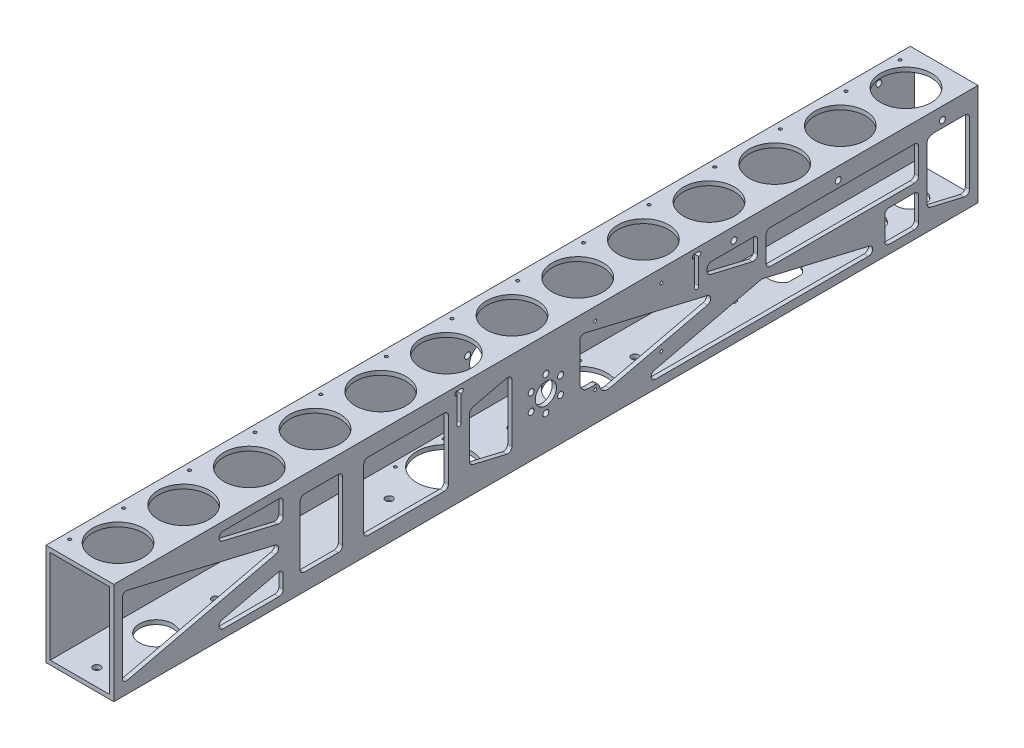
SolidWorks part; units mm, degrees
material "6061-T6 (SS)"
ref_plane "Front Plane" through (0, 0, 0) normal (0, 0, 1) x (1, 0, 0)
ref_plane "Top Plane" through (0, 0, 0) normal (0, 1, 0) x (1, 0, 0)
ref_plane "Right Plane" through (0, 0, 0) normal (1, 0, 0) x (0, 0, -1)
sketch "Sketch1" plane through (0, 0, 0) normal (0, 0, 1) x (1, 0, 0)
  line L0 (3.175, 3.175) -> (3.175, 73.025)
  line L1 (0, 0) -> (50.8, 0)
  line L2 (0, 0) -> (0, 76.2)
  line L3 (0, 76.2) -> (50.8, 76.2)
  line L4 (50.8, 0) -> (50.8, 76.2)
  line L5 (3.175, 73.025) -> (47.625, 73.025)
  line L6 (47.625, 3.175) -> (47.625, 73.025)
  line L7 (3.175, 3.175) -> (47.625, 3.175)
  dimension "D1" = 76.2
  dimension "D2" = 50.8
  dimension "D3" = 3.175
extrude "Boss-Extrude1" add sketch "Sketch1" along normal blind 647.7
sketch "Sketch2" plane through (50.8, 0, 0) normal (1, 0, 0) x (0, 0, -1)
  line L0 (-323.85, 76.2) -> (-323.85, 0) construction
  line L1 (-647.7, 76.2) -> (0, 76.2) construction
  line L2 (-647.7, 0) -> (0, 0) construction
  line L3 (-121.0655, 35.0094) -> (-10.2522, 8.9357)
  line L4 (-322.3956, 82.3812) -> (1.4544, 6.1812) construction
  line L5 (-649.1544, 6.1812) -> (-325.3044, 82.3812) construction
  line L6 (-646.2456, 82.3812) -> (-322.3956, 6.1812) construction
  line L7 (-649.1544, 70.0188) -> (-325.3044, -6.1812) construction
  line L8 (-647.7, 76.2) -> (-323.85, 0) construction
  line L9 (-647.7, 0) -> (-323.85, 76.2) construction
  line L10 (-323.85, 76.2) -> (0, 0) construction
  line L11 (-323.85, 0) -> (0, 76.2) construction
  line L12 (-6.35, 6.35) -> (-6.35, 69.85)
  line L13 (-6.35, 69.85) -> (-641.35, 69.85)
  line L14 (-641.35, 69.85) -> (-641.35, 6.35)
  line L15 (-641.35, 6.35) -> (-6.35, 6.35)
  line L16 (-6.35, 12.0263) -> (-6.35, 64.1737)
  line L17 (-646.2456, -6.1812) -> (-322.3956, 70.0188) construction
  line L18 (-641.35, 64.1737) -> (-641.35, 12.0263)
  line L19 (-641.35, 6.35) -> (-620.7125, 6.35)
  line L20 (-322.3956, -6.1812) -> (1.4544, 70.0188) construction
  line L21 (-325.3044, 6.1812) -> (-1.4544, 82.3812) construction
  line L22 (-161.1978, 44.7945) -> (-81.3408, 63.5844)
  line L23 (-161.1978, 31.4055) -> (-81.3408, 12.6156)
  line L24 (-241.782, 69.85) -> (-82.068, 69.85)
  line L25 (-647.7, 69.85) -> (0, 69.85)
  line L26 (-641.35, 69.85) -> (-620.7125, 69.85)
  line L27 (-241.782, 6.35) -> (-82.068, 6.35)
  line L28 (-566.3592, 63.5844) -> (-486.5022, 44.7945)
  line L29 (-637.4478, 67.2643) -> (-526.6345, 41.1906)
  line L30 (-637.4478, 8.9357) -> (-526.6345, 35.0094)
  line L31 (-566.3592, 12.6156) -> (-486.5022, 31.4055)
  line L32 (-242.5092, 63.5844) -> (-162.6522, 44.7945)
  line L33 (-325.3044, 70.0188) -> (-323.85, 69.6766)
  line L34 (-294.5478, 13.418) -> (-202.7845, 35.0094)
  line L35 (-242.5092, 12.6156) -> (-162.6522, 31.4055)
  line L36 (-349.25, 59.6914) -> (-349.25, 16.5086)
  line L37 (-298.45, 59.6914) -> (-298.45, 16.5086)
  line L38 (-294.5478, 62.782) -> (-202.7845, 41.1906)
  line L39 (-121.0655, 41.1906) -> (-10.2522, 67.2643)
  line L40 (-325.3044, 70.0188) -> (-1.4544, -6.1812) construction
  line L41 (-485.0478, 44.7945) -> (-405.1908, 63.5844)
  line L42 (-444.9155, 35.0094) -> (-353.1522, 13.418)
  line L43 (-444.9155, 41.1906) -> (-353.1522, 62.782)
  line L44 (-485.0478, 31.4055) -> (-405.1908, 12.6156)
  line L45 (-565.632, 69.85) -> (-405.918, 69.85)
  line L46 (-565.632, 6.35) -> (-405.918, 6.35)
  line L47 (-26.9875, 6.35) -> (-6.35, 6.35)
  line L48 (-26.9875, 69.85) -> (-6.35, 69.85)
  arc A0 (-405.918, 6.35) -> (-405.1908, 12.6156) centre (-405.918, 9.525) ccw
  arc A1 (-565.632, 6.35) -> (-566.3592, 12.6156) centre (-565.632, 9.525) cw
  arc A2 (-641.35, 64.1737) -> (-637.4478, 67.2643) centre (-638.175, 64.1737) cw
  arc A3 (-637.4478, 8.9357) -> (-641.35, 12.0263) centre (-638.175, 12.0263) cw
  arc A4 (-82.068, 6.35) -> (-81.3408, 12.6156) centre (-82.068, 9.525) ccw
  arc A5 (-241.782, 6.35) -> (-242.5092, 12.6156) centre (-241.782, 9.525) cw
  arc A6 (-6.35, 12.0263) -> (-10.2522, 8.9357) centre (-9.525, 12.0263) cw
  arc A7 (-6.35, 64.1737) -> (-10.2522, 67.2643) centre (-9.525, 64.1737) ccw
  arc A8 (-81.3408, 63.5844) -> (-82.068, 69.85) centre (-82.068, 66.675) ccw
  arc A9 (-242.5092, 63.5844) -> (-241.782, 69.85) centre (-241.782, 66.675) cw
  arc A10 (-121.0655, 41.1906) -> (-121.0655, 35.0094) centre (-120.3383, 38.1) ccw
  arc A11 (-161.1978, 31.4055) -> (-162.6522, 31.4055) centre (-161.925, 28.3149) ccw
  arc A12 (-161.1978, 44.7945) -> (-162.6522, 44.7945) centre (-161.925, 47.8851) cw
  arc A13 (-202.7845, 35.0094) -> (-202.7845, 41.1906) centre (-203.5117, 38.1) ccw
  arc A14 (-294.5478, 13.418) -> (-298.45, 16.5086) centre (-295.275, 16.5086) cw
  arc A15 (-294.5478, 62.782) -> (-298.45, 59.6914) centre (-295.275, 59.6914) ccw
  arc A16 (-353.1522, 62.782) -> (-349.25, 59.6914) centre (-352.425, 59.6914) cw
  arc A17 (-349.25, 16.5086) -> (-353.1522, 13.418) centre (-352.425, 16.5086) cw
  arc A18 (-485.0478, 31.4055) -> (-486.5022, 31.4055) centre (-485.775, 28.3149) ccw
  arc A19 (-526.6345, 35.0094) -> (-526.6345, 41.1906) centre (-527.3617, 38.1) ccw
  arc A20 (-444.9155, 35.0094) -> (-444.9155, 41.1906) centre (-444.1883, 38.1) cw
  arc A21 (-485.0478, 44.7945) -> (-486.5022, 44.7945) centre (-485.775, 47.8851) cw
  arc A22 (-405.1908, 63.5844) -> (-405.918, 69.85) centre (-405.918, 66.675) ccw
  arc A23 (-566.3592, 63.5844) -> (-565.632, 69.85) centre (-565.632, 66.675) cw
  point P69 (-592.988, 6.35)
  point P92 (-161.925, 44.6234)
  point P99 (-298.45, 63.7001)
  point P106 (-485.775, 31.5766)
  point P111 (-458.0505, 38.1)
  point P118 (-592.988, 69.85)
  dimension "D13" = 3.175
  dimension "D11" = 25.4
  dimension "D12" = 25.4
  dimension "D1" = 6.35
  dimension "D2" = 6.35
  dimension "D3" = 6.35
  dimension "D4" = 6.35
  dimension "D5" = 6.35
  dimension "D6" = 6.35
  dimension "D7" = 6.35
  dimension "D8" = 6.35
  dimension "D9" = 6.35
  dimension "D10" = 6.35
extrude "Cut-Extrude1" cut sketch "Sketch2" against normal through all contours A23 L28 A21 L41 A22 L45 | L30 A19 L29 A2 L18 A3 | L44 A18 L31 A1 L46 A0 | A20 L42 A17 L36 A16 L43 | L38 A15 L37 A14 L34 A13 | A12 L22 A8 L24 A9 L32 | L23 A11 L35 A5 L27 A4 | L39 A10 L3 A6 L16 A7
sketch "Sketch3" plane through (0, 76.2, 0) normal (0, 1, 0) x (1, 0, 0)
  line L0 (50.8, -647.7) -> (0, -647.7) construction
  line L1 (0, -647.7) -> (0, 0) construction
  circle A0 centre (25.4, -603.25) radius 19.05
  circle A1 centre (25.4, -552.45) radius 19.05
  circle A6 centre (25.4, -298.45) radius 19.05
  circle A7 centre (25.4, -247.65) radius 19.05
  circle A8 centre (25.4, -196.85) radius 19.05
  circle A10 centre (25.4, -95.25) radius 19.05
  circle A11 centre (25.4, -44.45) radius 19.05
  circle A12 centre (25.4, -501.65) radius 19.05
  circle A13 centre (25.4, -146.05) radius 19.05
  circle A14 centre (25.4, -349.25) radius 19.05
  circle A15 centre (25.4, -400.05) radius 19.05
  circle A16 centre (25.4, -450.85) radius 19.05
  dimension "D1" = 38.1
  dimension "D2" = 44.45
  dimension "D3" = 25.4
  dimension "D4" = 12
extrude "Cut-Extrude2" [suppressed] cut sketch "Sketch3" against normal through all
sketch "Sketch4" plane through (50.8, 0, 0) normal (1, 0, 0) x (0, 0, -1)
  line L0 (-647.7, 76.2) -> (0, 76.2) construction
  line L1 (-323.85, 76.2) -> (-323.85, 0) construction
  line L2 (-647.7, 0) -> (0, 0) construction
  circle A0 centre (-323.85, 38.1) radius 7.9375
  dimension "D2" = 15.875
  dimension "D1" = 38.1
extrude "Cut-Extrude3" cut sketch "Sketch4" against normal through all
sketch "Sketch5" plane through (0, 0, 0) normal (-1, 0, 0) x (0, 0, 1)
  circle A0 centre (323.85, 38.1) radius 9.525
  dimension "D1" = 19.05
extrude "Cut-Extrude4" cut sketch "Sketch5" against normal up to next
hole_wizard "#8 Clearance Hole1" positions "Sketch7" profile "Sketch6" hole size "#8" standard "Ansi Inch" end condition through all
sketch "Sketch7" plane through (0, 0, 0) normal (-1, 0, 0) x (0, 0, 1)
  line L0 (647.7, 76.2) -> (0, 76.2) construction
  line L1 (323.85, 76.2) -> (323.85, 0) construction
  line L2 (647.7, 0) -> (0, 0) construction
  circle A0 centre (323.85, 38.1) radius 9.525 construction
  point P0 (323.85, 50.8)
  point P15 (323.85, 76.2)
  dimension "D1" = 12.7
sketch "Sketch6" plane through (0, 50.8, 323.85) normal (0, 1, 0) x (0, 0, 1)
  line L0 (0, 0) -> (0, 50.8)
  line L1 (0, 50.8) -> (2.2479, 50.8)
  line L2 (2.2479, 50.8) -> (2.2479, 0)
  line L5 (2.2479, 0) -> (0, 0)
  line L11 (0, -6.35) -> (0, 107.95) construction
  dimension "Thru Hole Dia." = 4.4958
  dimension "Thru Hole Depth" = 50.8
pattern_circular "CirPattern1" count 6 over 360 about axis through (0, 38.1, 323.85) along (1, 0, 0) of "#8 Clearance Hole1"
hole_wizard "1/4-28 Tapped Hole1" positions "Sketch9" profile "Sketch8" tap size "1/4-28" standard "Ansi Inch"
sketch "Sketch9" plane through (0, 76.2, 0) normal (0, 1, 0) x (-1, 0, 0)
  line L0 (-25.4, 647.7) -> (-25.4, 0) construction
  line L1 (-50.8, 647.7) -> (0, 647.7) construction
  line L2 (-50.8, 0) -> (0, 0) construction
  point P0 (-25.4, 498.475)
  point P1 (-25.4, 323.85)
  point P5 (-25.4, 149.225)
  point P20 (-25.4, 323.85)
  dimension "D1" = 149.225
  dimension "D2" = 149.225
sketch "Sketch8" plane through (25.4, 76.2, 498.475) normal (1, 0, 0) x (0, 0, 1)
  line L0 (0, 0) -> (0, 76.2)
  line L1 (0, 76.2) -> (2.7051, 76.2)
  line L2 (2.7051, 76.2) -> (2.7051, 0)
  line L5 (2.7051, 0) -> (0, 0)
  line L11 (0, -6.35) -> (0, 107.95) construction
  dimension "Thru Tap Drill Dia." = 5.4102
  dimension "Thru Tap Drill Depth" = 76.2
cosmetic thread "Hole Thread1" [suppressed]
cosmetic thread "Hole Thread2" [suppressed]
cosmetic thread "Hole Thread3" [suppressed]
sketch "Sketch10" plane through (50.8, 0, 0) normal (1, 0, 0) x (0, 0, -1)
  line L0 (-647.7, 0) -> (0, 0) construction
  line L1 (-520.7, 0) -> (-463.55, 0)
  line L2 (-520.7, 0) -> (-520.7, 76.2)
  line L3 (-520.7, 76.2) -> (-463.55, 76.2)
  line L4 (-463.55, 0) -> (-463.55, 76.2)
  line L5 (-647.7, 76.2) -> (0, 76.2) construction
  line L6 (-647.7, 0) -> (-647.7, 76.2) construction
  dimension "D1" = 127
  dimension "D2" = 57.15
extrude "Boss-Extrude2" add sketch "Sketch10" against normal blind 3.175
sketch "Sketch12" plane through (0, 76.2, 0) normal (0, 1, 0) x (1, 0, 0)
  line L0 (0, -647.7) -> (0, 0) construction
  line L1 (7.1374, -291.3126) -> (43.6626, -291.3126) construction
  line L2 (7.1374, -291.3126) -> (7.1374, -254.7874) construction
  line L3 (7.1374, -254.7874) -> (43.6626, -254.7874) construction
  line L4 (43.6626, -291.3126) -> (43.6626, -254.7874) construction
  line L5 (7.1374, -291.3126) -> (43.6626, -254.7874) construction
  line L6 (7.1374, -254.7874) -> (43.6626, -291.3126) construction
  line L9 (50.8, 0) -> (0, 0) construction
  line L10 (7.1374, -392.9126) -> (43.6626, -392.9126) construction
  line L11 (7.1374, -392.9126) -> (7.1374, -356.3874) construction
  line L12 (7.1374, -356.3874) -> (43.6626, -356.3874) construction
  line L13 (43.6626, -392.9126) -> (43.6626, -356.3874) construction
  line L14 (7.1374, -392.9126) -> (43.6626, -356.3874) construction
  line L15 (7.1374, -356.3874) -> (43.6626, -392.9126) construction
  line L16 (7.1374, -323.85) -> (43.6626, -323.85) construction
  line L17 (25.4, -293.497) -> (25.4, -354.203) construction
  line L19 (25.4, 25.4) -> (25.4, -622.3) construction
  line L20 (25.4, -76.2) -> (25.4, -723.9) construction
  circle A0 centre (25.4, -273.05) radius 20.447
  circle A1 centre (25.4, -374.65) radius 20.447
  point P0 (25.4, -273.05)
  point P5 (25.4, -323.85)
  point P15 (25.4, -374.65)
  dimension "D3" = 40.894
  dimension "D5" = 25.4
  dimension "D7" = 323.85
  dimension "D1" = 36.5252
  dimension "D2" = 36.5252
  dimension "D6" = 101.6
  dimension "D4" = 2
sketch "Sketch17" plane through (50.8, 0, 0) normal (1, 0, 0) x (0, 0, -1)
  line L0 (-492.125, 76.2) -> (-492.125, 0) construction
  line L1 (-647.7, 76.2) -> (0, 76.2) construction
  line L2 (-647.7, 0) -> (0, 0) construction
  line L3 (-647.7, 0) -> (-647.7, 76.2) construction
  line L6 (-508, 12.7) -> (-476.25, 12.7)
  line L7 (-508, 12.7) -> (-508, 63.5)
  line L8 (-508, 63.5) -> (-476.25, 63.5)
  line L9 (-476.25, 12.7) -> (-476.25, 63.5)
  line L10 (-508, 12.7) -> (-476.25, 63.5) construction
  line L11 (-508, 63.5) -> (-476.25, 12.7) construction
  point P8 (-492.125, 38.1)
  dimension "D1" = 139.7
  dimension "D2" = 50.8
  dimension "D3" = 31.75
extrude "Cut-Extrude6" cut sketch "Sketch17" against normal up to next
sketch "Sketch18" plane through (0, 76.2, 0) normal (0, 1, 0) x (1, 0, 0)
  line L0 (25.4, 0) -> (25.4, -647.7) construction
  line L1 (50.8, 0) -> (0, 0) construction
  line L2 (50.8, -647.7) -> (0, -647.7) construction
  line L3 (34.4043, -115.4433) -> (34.4043, -125.8567)
  arc A0 (34.4043, -115.4433) -> (34.4043, -125.8567) centre (25.4, -120.65) ccw
  dimension "D1" = 20.8026
  dimension "D2" = 120.65
  dimension "D3" = 9.0043
sketch "Sketch19" plane through (0, 76.2, 0) normal (0, 1, 0) x (1, 0, 0)
  line L0 (50.8, -647.7) -> (50.8, 0) construction
  line L1 (15.24, -9.525) -> (35.56, -9.525)
  line L2 (8.89, -15.875) -> (8.89, -130.175)
  line L3 (15.24, -136.525) -> (35.56, -136.525)
  line L4 (41.91, -15.875) -> (41.91, -130.175)
  line L5 (0, -647.7) -> (0, 0) construction
  arc A0 (35.56, -136.525) -> (41.91, -130.175) centre (35.56, -130.175) ccw
  arc A1 (8.89, -130.175) -> (15.24, -136.525) centre (15.24, -130.175) ccw
  arc A2 (35.56, -9.525) -> (41.91, -15.875) centre (35.56, -15.875) cw
  arc A3 (15.24, -9.525) -> (8.89, -15.875) centre (15.24, -15.875) ccw
  point P12 (41.91, -136.525)
  point P17 (41.91, -9.525)
  dimension "D5" = 6.35
  dimension "D3" = 15.875
  dimension "D1" = 8.89
  dimension "D2" = 8.89
  dimension "D4" = 127
ref_plane "Plane1" through (0, 38.1, 0) normal (0, 1, 0) x (-1, 0, 0)
sketch "Sketch20" [suppressed] plane through (0, 0, 0) normal (0, -1, 0) x (1, 0, 0)
  line L0 (25.4, 647.7) -> (25.4, 498.475) construction
  line L1 (0, 647.7) -> (50.8, 647.7) construction
  line L3 (13.0937, 603.6437) -> (37.7063, 603.6437) construction
  line L4 (13.0937, 603.6437) -> (13.0937, 628.2563) construction
  line L5 (13.0937, 628.2563) -> (37.7063, 628.2563) construction
  line L6 (37.7063, 603.6437) -> (37.7063, 628.2563) construction
  line L7 (13.0937, 603.6437) -> (37.7063, 628.2563) construction
  line L8 (13.0937, 628.2563) -> (37.7063, 603.6437) construction
  circle A0 centre (25.4, 615.95) radius 12.4333
  point P5 (25.4, 615.95)
  dimension "D3" = 24.8666
  dimension "D1" = 24.6126
  dimension "D2" = 24.6126
  dimension "D4" = 31.75
sketch "Sketch21" plane through (0, 0, 0) normal (0, -1, 0) x (1, 0, 0)
  circle A0 centre (25.4, 374.65) radius 20.447 construction
  circle A1 centre (25.4, 273.05) radius 20.447 construction
  circle A2 centre (25.4, 374.65) radius 20.447
  circle A3 centre (25.4, 273.05) radius 20.447
extrude "Cut-Extrude10" cut sketch "Sketch21" against normal up to next
hole_wizard "#4-40 Tapped Hole1" positions "Sketch23" profile "Sketch22" tap size "#4-40" standard "Ansi Inch" end condition up to next
sketch "Sketch23" plane through (0, 0, 0) normal (0, -1, 0) x (1, 0, 0)
  point P1 (7.1374, 392.9126)
  point P4 (43.6626, 392.9126)
  point P7 (7.1374, 356.3874)
  point P10 (43.6626, 356.3874)
  point P13 (7.1374, 291.3126)
  point P16 (43.6626, 291.3126)
  point P19 (7.1374, 254.7874)
  point P22 (43.6626, 254.7874)
cosmetic thread "Hole Thread4"
cosmetic thread "Hole Thread5"
cosmetic thread "Hole Thread6"
cosmetic thread "Hole Thread7"
cosmetic thread "Hole Thread8"
cosmetic thread "Hole Thread9"
cosmetic thread "Hole Thread10"
cosmetic thread "Hole Thread11"
sketch "Sketch22" plane through (7.1374, 0, 392.9126) normal (1, 0, 0) x (0, 0, -1)
  line L0 (0, 0) -> (0, 3.175)
  line L1 (0, 3.175) -> (1.1303, 3.175)
  line L2 (1.1303, 3.175) -> (1.1303, 0)
  line L5 (1.1303, 0) -> (0, 0)
  line L11 (0, -6.35) -> (0, 107.95) construction
  dimension "Thru Tap Drill Dia." = 2.2606
  dimension "Thru Tap Drill Depth" = 3.175
sketch "Sketch24" plane through (0, 0, 0) normal (0, -1, 0) x (1, 0, 0)
  line L0 (34.4043, 115.4433) -> (34.4043, 125.8567) construction
  line L1 (34.4043, 115.4433) -> (34.4043, 125.8567)
  arc A0 (34.4043, 125.8567) -> (34.4043, 115.4433) centre (25.4, 120.65) ccw construction
  arc A1 (34.4043, 125.8567) -> (34.4043, 115.4433) centre (25.4, 120.65) ccw
extrude "Cut-Extrude11" cut sketch "Sketch24" against normal up to next
pattern_linear "LPattern1" count 4 spacing 31.75 along (0, 0, -1) of "Cut-Extrude11"
sketch "Sketch25" plane through (0, 0, 0) normal (0, -1, 0) x (1, 0, 0)
  line L0 (15.24, 136.525) -> (35.56, 136.525) construction
  line L1 (8.89, 15.875) -> (8.89, 130.175) construction
  line L2 (15.24, 9.525) -> (35.56, 9.525) construction
  line L3 (41.91, 15.875) -> (41.91, 130.175) construction
  line L4 (0, 0) -> (50.8, 0)
  line L5 (50.8, 0) -> (50.8, 647.7)
  line L6 (50.8, 647.7) -> (0, 647.7)
  line L7 (0, 647.7) -> (0, 0)
  line L8 (0, 0) -> (50.8, 0)
  line L9 (50.8, 0) -> (50.8, 647.7)
  line L10 (50.8, 647.7) -> (0, 647.7)
  line L11 (0, 647.7) -> (0, 0)
  line L12 (15.24, 136.525) -> (35.56, 136.525)
  line L13 (8.89, 15.875) -> (8.89, 130.175)
  line L14 (15.24, 9.525) -> (35.56, 9.525)
  line L15 (41.91, 15.875) -> (41.91, 130.175)
  arc A0 (15.24, 136.525) -> (8.89, 130.175) centre (15.24, 130.175) ccw construction
  arc A1 (8.89, 15.875) -> (15.24, 9.525) centre (15.24, 15.875) ccw construction
  arc A2 (35.56, 9.525) -> (41.91, 15.875) centre (35.56, 15.875) ccw construction
  arc A3 (41.91, 130.175) -> (35.56, 136.525) centre (35.56, 130.175) ccw construction
  arc A4 (15.24, 136.525) -> (8.89, 130.175) centre (15.24, 130.175) ccw
  arc A5 (8.89, 15.875) -> (15.24, 9.525) centre (15.24, 15.875) ccw
  arc A6 (35.56, 9.525) -> (41.91, 15.875) centre (35.56, 15.875) ccw
  arc A7 (41.91, 130.175) -> (35.56, 136.525) centre (35.56, 130.175) ccw
  dimension "D1" = 0
extrude "Cut-Extrude12" cut sketch "Sketch25" against normal blind 1.5875 flip side to cut
hole_wizard "1/4-28 Tapped Hole2" positions "Sketch27" profile "Sketch26" tap size "1/4-28" standard "Ansi Inch" end condition up to next
sketch "Sketch27" plane through (14.4115, 0, -20.3004) normal (0, -1, 0) x (1, 0, 0)
  line L0 (10.9885, 20.3004) -> (10.9885, 668.0004) construction
  line L3 (-14.4115, 668.0004) -> (36.3885, 668.0004) construction
  line L4 (-14.4115, 20.3004) -> (36.3885, 20.3004) construction
  line L5 (-14.4115, 668.0004) -> (-14.4115, 20.3004) construction
  point P10 (10.9885, 179.0504)
  point P12 (10.9885, 252.0754)
  point P14 (10.9885, 344.1504)
  point P16 (10.9885, 436.2254)
  point P18 (10.9885, 566.4004)
  point P20 (10.9885, 655.3004)
  dimension "D1" = 158.75
  dimension "D2" = 73.025
  dimension "D3" = 92.075
  dimension "D4" = 130.175
  dimension "D5" = 88.9
  dimension "D6" = 25.4
sketch "Sketch26" plane through (25.4, 0, 158.75) normal (1, 0, 0) x (0, 0, -1)
  line L0 (0, 0) -> (0, 3.175)
  line L1 (0, 3.175) -> (2.7051, 3.175)
  line L2 (2.7051, 3.175) -> (2.7051, 0)
  line L5 (2.7051, 0) -> (0, 0)
  line L11 (0, -6.35) -> (0, 107.95) construction
  dimension "Thru Tap Drill Dia." = 5.4102
  dimension "Thru Tap Drill Depth" = 3.175
cosmetic thread "Hole Thread18"
cosmetic thread "Hole Thread19"
cosmetic thread "Hole Thread20"
cosmetic thread "Hole Thread22"
cosmetic thread "Hole Thread23"
cosmetic thread "Hole Thread24"
sketch "Sketch28" plane through (0, 0, 0) normal (0, -1, 0) x (1, 0, 0)
  line L1 (0, 647.7) -> (0, 0) construction
  circle A0 centre (25.4, 195.2625) radius 19.05
  circle A1 centre (25.4, 455.6125) radius 19.05
  circle A2 centre (25.4, 506.4125) radius 19.05
  circle A3 centre (25.4, 590.55) radius 19.05
  circle A6 centre (25.4, 635) radius 2.7051 construction
  circle A8 centre (25.4, 546.1) radius 2.7051 construction
  circle A9 centre (25.4, 231.775) radius 2.7051 construction
  dimension "D1" = 38.1
  dimension "D5" = 39.6875
  dimension "D2" = 44.45
  dimension "D3" = 25.4
  dimension "D4" = 50.8
  dimension "D6" = 36.5125
extrude "Cut-Extrude13" cut sketch "Sketch28" against normal up to next
sketch "Sketch29" plane through (0, 76.2, 0) normal (0, 1, 0) x (1, 0, 0)
  line L0 (0, -647.7) -> (0, 0) construction
  line L1 (50.8, 0) -> (0, 0) construction
  circle A0 centre (25.4, -28.575) radius 19.05
  circle A1 centre (25.4, -77.7875) radius 19.05
  circle A2 centre (25.4, -127) radius 19.05
  circle A3 centre (25.4, -176.2125) radius 19.05
  circle A4 centre (25.4, -225.425) radius 19.05
  circle A5 centre (25.4, -274.6375) radius 19.05
  circle A6 centre (25.4, -323.85) radius 19.05
  circle A7 centre (25.4, -373.0625) radius 19.05
  circle A8 centre (25.4, -422.275) radius 19.05
  circle A9 centre (25.4, -471.4875) radius 19.05
  circle A10 centre (25.4, -520.7) radius 19.05
  circle A11 centre (25.4, -569.9125) radius 19.05
  circle A12 centre (25.4, -619.125) radius 19.05
  dimension "D1" = 38.1
  dimension "D2" = 25.4
  dimension "D3" = 28.575
  dimension "D5" = 49.2125
  dimension "D4" = 13
extrude "Cut-Extrude14" cut sketch "Sketch29" against normal up to next
sketch "Sketch30" plane through (50.8, 0, 0) normal (1, 0, 0) x (0, 0, -1)
  line L0 (-388.9375, 71.4375) -> (-388.9375, 50.8) construction
  line L1 (-387.35, 71.4375) -> (-387.35, 50.8)
  line L2 (-390.525, 71.4375) -> (-390.525, 50.8)
  line L3 (-647.7, 0) -> (-647.7, 76.2) construction
  line L4 (-647.7, 76.2) -> (0, 76.2) construction
  line L8 (-381, 19.9705) -> (-381, 56.2295)
  line L9 (-444.9155, 35.0094) -> (-353.1522, 13.418) construction
  line L10 (-444.9155, 41.1906) -> (-353.1522, 62.782) construction
  line L13 (-395.2875, 52.8678) -> (-381, 56.2295)
  line L14 (-395.2875, 23.3322) -> (-381, 19.9705)
  line L15 (-395.2875, 52.8678) -> (-395.2875, 23.3322)
  arc A0 (-387.35, 71.4375) -> (-390.525, 71.4375) centre (-388.9375, 71.4375) ccw
  arc A1 (-390.525, 50.8) -> (-387.35, 50.8) centre (-388.9375, 50.8) ccw
  point P2 (-388.9375, 61.1187)
  dimension "D1" = 260.35
  dimension "D2" = 3.175
  dimension "D3" = 4.7625
  dimension "D4" = 20.6375
  dimension "D6" = 6.35
  dimension "D7" = 6.35
extrude "Boss-Extrude3" add sketch "Sketch30" against normal up to surface (3.175 mm away) up to face at (47.625, 38.1, 492.125)
sketch "Sketch32" plane through (0, 0, 0) normal (-1, 0, 0) x (0, 0, 1)
  line L0 (395.2875, 52.8678) -> (395.2875, 23.3322) construction
  line L1 (395.2875, 52.8678) -> (395.2875, 23.3322)
  line L3 (444.9155, 41.1906) -> (353.1522, 62.782) construction
  line L4 (381, 19.9705) -> (381, 56.2295) construction
  line L5 (444.9155, 35.0094) -> (353.1522, 13.418) construction
  line L9 (395.2875, 52.8678) -> (381, 56.2295)
  line L10 (381, 19.9705) -> (381, 56.2295)
  line L11 (395.2875, 23.3322) -> (381, 19.9705)
extrude "Boss-Extrude4" add sketch "Sketch32" against normal up to surface (3.175 mm away) up to face at (3.175, 44.45, 332.6006)
sketch "Sketch33" plane through (50.8, 0, 0) normal (1, 0, 0) x (0, 0, -1)
  line L0 (-209.296, 76.2) -> (-209.296, 0) construction
  line L2 (-647.7, 76.2) -> (0, 76.2) construction
  line L3 (-647.7, 0) -> (0, 0) construction
  line L8 (-202.946, 69.85) -> (-202.946, 54.2754)
  line L9 (-241.782, 69.85) -> (-82.068, 69.85) construction
  line L12 (-242.5092, 63.5844) -> (-162.6522, 44.7945) construction
  line L13 (-241.782, 69.85) -> (-202.946, 69.85)
  line L14 (-242.5092, 63.5844) -> (-202.946, 54.2754)
  line L15 (0, 76.2) -> (0, 0) construction
  arc A0 (-241.782, 69.85) -> (-242.5092, 63.5844) centre (-241.782, 66.675) ccw construction
  arc A1 (-241.782, 69.85) -> (-242.5092, 63.5844) centre (-241.782, 66.675) ccw
  dimension "D1" = 209.296
  dimension "D2" = 6.35
extrude "Boss-Extrude5" add sketch "Sketch33" against normal up to surface (3.175 mm away) up to face at (47.625, 38.1, 323.85)
sketch "Sketch34" plane through (0, 0, 0) normal (-1, 0, 0) x (0, 0, 1)
  line L3 (241.782, 69.85) -> (82.068, 69.85) construction
  line L4 (202.946, 54.2754) -> (202.946, 69.85) construction
  line L9 (242.5092, 63.5844) -> (162.6522, 44.7945) construction
  line L11 (241.782, 69.85) -> (202.946, 69.85)
  line L12 (242.5092, 63.5844) -> (202.946, 54.2754)
  line L13 (202.946, 54.2754) -> (202.946, 69.85)
  arc A0 (242.5092, 63.5844) -> (241.782, 69.85) centre (241.782, 66.675) ccw construction
  arc A1 (242.5092, 63.5844) -> (241.782, 69.85) centre (241.782, 66.675) ccw
extrude "Boss-Extrude6" add sketch "Sketch34" against normal up to surface (3.175 mm away) up to face at (3.175, 38.1, 420.7134)
sketch "Sketch31" plane through (50.8, 0, 0) normal (1, 0, 0) x (0, 0, -1)
  line L0 (-390.525, 71.4375) -> (-390.525, 50.8) construction
  line L1 (-387.35, 71.4375) -> (-387.35, 50.8) construction
  line L2 (-390.525, 69.85) -> (-390.525, 50.8)
  line L3 (-387.35, 69.85) -> (-387.35, 50.8)
  line L4 (-390.525, 71.4375) -> (-387.35, 71.4375) construction
  line L5 (-390.525, 73.025) -> (-387.35, 73.025)
  line L7 (-212.471, 69.8501) -> (-212.471, 50.8001)
  line L8 (-209.296, 69.8501) -> (-209.296, 50.8001)
  line L9 (-212.471, 73.0251) -> (-209.296, 73.0251)
  line L10 (-212.471, 71.4376) -> (-209.296, 71.4376) construction
  arc A0 (-387.35, 71.4375) -> (-390.525, 71.4375) centre (-388.9375, 71.4375) ccw construction
  arc A1 (-390.525, 50.8) -> (-387.35, 50.8) centre (-388.9375, 50.8) ccw construction
  arc A2 (-212.471, 50.8001) -> (-209.296, 50.8001) centre (-210.8835, 50.8001) ccw
  arc A3 (-390.525, 50.8) -> (-387.35, 50.8) centre (-388.9375, 50.8) ccw
  arc A4 (-390.525, 73.025) -> (-390.525, 69.85) centre (-390.525, 71.4375) ccw
  arc A5 (-387.35, 69.85) -> (-387.35, 73.025) centre (-387.35, 71.4375) ccw
  arc A6 (-212.471, 73.0251) -> (-212.471, 69.8501) centre (-212.471, 71.4376) ccw
  arc A7 (-209.296, 69.8501) -> (-209.296, 73.0251) centre (-209.296, 71.4376) ccw
  point P8 (-388.9375, 71.4375)
  point P19 (-210.8835, 71.4376)
  dimension "D3" = 1.5875
  dimension "D1" = 3.175
  dimension "D2" = 3.175
  dimension "D4" = 1.5875
  dimension "D5" = 2
  dimension "D6" = 178.054
extrude "Cut-Extrude15" cut sketch "Sketch31" against normal up to next
fillet "Fillet1" radius 3.175 24 edges at (49.2125, 6.35, 520.7) (49.2125, 26.3472, 463.55) (49.2125, 23.3589, 520.7) (49.2125, 6.35, 463.55) (49.2125, 49.8528, 463.55) (49.2125, 69.85, 463.55) (49.2125, 52.8411, 520.7) (49.2125, 69.85, 520.7) (49.2125, 12.7, 476.25) (49.2125, 12.7, 508) (49.2125, 63.5, 476.25) (49.2125, 63.5, 508) (49.2125, 19.9705, 381) (49.2125, 56.2295, 381) (1.5875, 19.9705, 381) (1.5875, 56.2295, 381) (49.2125, 23.3322, 395.2875) (49.2125, 52.8678, 395.2875) (1.5875, 52.8678, 395.2875) (1.5875, 23.3322, 395.2875) (49.2125, 69.85, 202.946) (49.2125, 54.2754, 202.946) (1.5875, 69.85, 202.946) (1.5875, 54.2754, 202.946)
sketch "Sketch36" plane through (50.8, 0, 0) normal (1, 0, 0) x (0, 0, -1)
  line L0 (-647.7, 76.2) -> (0, 76.2) construction
  line L1 (-286.8839, 22.225) -> (-237.3539, 22.225) construction
  line L2 (-286.8839, 22.225) -> (-286.8839, 66.675) construction
  line L3 (-286.8839, 66.675) -> (-237.3539, 66.675) construction
  line L4 (-237.3539, 22.225) -> (-237.3539, 66.675) construction
  line L5 (-286.8839, 22.225) -> (-237.3539, 66.675) construction
  line L6 (-286.8839, 66.675) -> (-237.3539, 22.225) construction
  line L7 (-286.8839, 25.4) -> (-298.45, 25.4)
  line L8 (-283.7089, 22.225) -> (-283.7089, 15.9684)
  line L9 (-298.45, 59.6914) -> (-298.45, 16.5086) construction
  line L10 (-294.5478, 13.418) -> (-202.7845, 35.0094) construction
  line L11 (-298.45, 25.4) -> (-298.45, 16.5086)
  line L12 (-294.5478, 13.418) -> (-283.7089, 15.9684)
  line L13 (-257.1182, 22.225) -> (-202.7845, 35.0094)
  arc A0 (-283.7089, 22.225) -> (-286.8839, 25.4) centre (-286.8839, 22.225) ccw
  arc A1 (-298.45, 16.5086) -> (-294.5478, 13.418) centre (-295.275, 16.5086) ccw construction
  arc A2 (-298.45, 16.5086) -> (-294.5478, 13.418) centre (-295.275, 16.5086) ccw
  point P0 (-262.1189, 44.45)
  dimension "D4" = 6.35
  dimension "D1" = 44.45
  dimension "D2" = 49.53
  dimension "D3" = 31.75
  dimension "D5" = 14.7411
extrude "Boss-Extrude7" add sketch "Sketch36" against normal up to surface (3.175 mm away) contours L11 A2 L12 L8 A0 L7 up to face at (47.625, 57.7441, 305.8954)
fillet "Fillet2" radius 6.35 2 edges at (49.2125, 15.9684, 283.7089) (49.2125, 25.4, 298.45)
hole_wizard "#4-40 Tapped Hole2" positions "Sketch38" profile "Sketch39" tap size "#4-40" standard "Ansi Inch" end condition up to next
sketch "Sketch38" plane through (50.8, 0, 0) normal (1, 0, 0) x (0, 0, -1)
  point P1 (-286.8839, 66.675)
  point P4 (-237.3539, 66.675)
  point P7 (-286.8839, 22.225)
  point P10 (-237.3539, 22.225)
sketch "Sketch39" plane through (50.8, 66.675, 286.8839) normal (0, 1, 0) x (0, 0, -1)
  line L0 (0, 0) -> (0, 3.175)
  line L1 (0, 3.175) -> (1.1303, 3.175)
  line L2 (1.1303, 3.175) -> (1.1303, 0)
  line L5 (1.1303, 0) -> (0, 0)
  line L11 (0, -6.35) -> (0, 107.95) construction
  dimension "Thread Major Dia." = 2.2606
  dimension "Thru Tap Drill Depth" = 3.175
sketch "Sketch40" plane through (0, 0, 0) normal (0, -1, 0) x (1, 0, 0)
  circle A0 centre (25.4, 590.55) radius 12.446
  circle A1 centre (25.4, 590.55) radius 19.05 construction
  circle A2 centre (25.4, 590.55) radius 19.05
  dimension "D1" = 24.892
extrude "Boss-Extrude8" add sketch "Sketch40" against normal up to surface (3.175 mm away) up to face at (25.4, 3.175, 609.6)
sketch "Sketch41" plane through (50.8, 0, 0) normal (1, 0, 0) x (0, 0, -1)
  line L0 (-202.946, 56.7901) -> (-202.946, 66.675) construction
  line L1 (0, 76.2) -> (-202.946, 76.2)
  line L2 (0, 76.2) -> (0, 61.9125)
  line L3 (0, 61.9125) -> (-202.946, 61.9125)
  line L4 (-202.946, 76.2) -> (-202.946, 61.9125)
  dimension "D1" = 14.2875
extrude "Boss-Extrude9" add sketch "Sketch41" against normal up to surface (3.175 mm away) up to face at (47.625, 66.675, 288.0142)
fillet "Fillet3" radius 3.175 4 edges at (49.2125, 61.9125, 202.946) (49.2125, 61.9125, 88.4464) (49.2125, 61.9125, 6.35) (49.2125, 61.9125, 32.9974)
hole_wizard "#8 Clearance Hole2" positions "Sketch43" profile "Sketch42" hole size "#8" standard "Ansi Inch" end condition up to next
sketch "Sketch43" plane through (50.8, 0, 0) normal (1, 0, 0) x (0, 0, -1)
  line L0 (-647.7, 76.2) -> (0, 76.2) construction
  line L1 (0, 0) -> (0, 76.2) construction
  point P0 (-26.67, 66.9925)
  point P1 (-104.775, 66.9925)
  point P3 (-182.88, 66.9925)
  dimension "D1" = 9.2075
  dimension "D2" = 26.67
  dimension "D3" = 78.105
  dimension "D4" = 78.105
sketch "Sketch42" plane through (50.8, 66.9925, 26.67) normal (0, 1, 0) x (0, 0, -1)
  line L0 (0, 0) -> (0, 3.175)
  line L1 (0, 3.175) -> (2.2479, 3.175)
  line L2 (2.2479, 3.175) -> (2.2479, 0)
  line L5 (2.2479, 0) -> (0, 0)
  line L11 (0, -6.35) -> (0, 107.95) construction
  dimension "Thru Hole Dia." = 4.4958
  dimension "Thru Hole Depth" = 3.175
sketch "Sketch44" plane through (0, 0, 0) normal (-1, 0, 0) x (0, 0, 1)
  line L0 (202.946, 66.675) -> (202.946, 56.7901) construction
  line L1 (0, 76.2) -> (202.946, 76.2)
  line L2 (0, 76.2) -> (0, 61.9125)
  line L3 (0, 61.9125) -> (202.946, 61.9125)
  line L4 (202.946, 76.2) -> (202.946, 61.9125)
  line L5 (199.771, 61.9125) -> (115.8024, 61.9125) construction
extrude "Boss-Extrude10" add sketch "Sketch44" against normal up to surface (3.175 mm away) up to face at (3.175, 58.8136, 161.4781)
fillet "Fillet4" radius 3.175 4 edges at (1.5875, 61.9125, 6.35) (1.5875, 61.9125, 32.9974) (1.5875, 61.9125, 88.4464) (1.5875, 61.9125, 202.946)
hole_wizard "#8 Clearance Hole3" positions "Sketch46" profile "Sketch47" hole size "#8" standard "Ansi Inch" end condition up to next
sketch "Sketch46" plane through (3.175, 0, 0) normal (1, 0, 0) x (0, 0, -1)
  point P0 (-26.67, 66.9925)
  point P4 (-104.775, 66.9925)
  point P7 (-182.88, 66.9925)
sketch "Sketch47" plane through (3.175, 66.9925, 26.67) normal (0, 1, 0) x (0, 0, -1)
  line L0 (0, 0) -> (0, 3.175)
  line L1 (0, 3.175) -> (2.2479, 3.175)
  line L2 (2.2479, 3.175) -> (2.2479, 0)
  line L5 (2.2479, 0) -> (0, 0)
  line L11 (0, -6.35) -> (0, 107.95) construction
  dimension "Thru Hole Dia." = 4.4958
  dimension "Thru Hole Depth" = 3.175
sketch "Sketch48" plane through (50.8, 0, 0) normal (1, 0, 0) x (0, 0, -1)
  line L0 (-199.771, 61.9125) -> (-115.8024, 61.9125) construction
  line L1 (-165.1, 61.9125) -> (-38.1, 61.9125)
  line L2 (-165.1, 61.9125) -> (-165.1, 35.0094)
  line L3 (-121.0655, 35.0094) -> (-10.2522, 8.9357) construction
  line L4 (-38.1, 61.9125) -> (-38.1, 15.4881)
  line L5 (0, 0) -> (0, 76.2) construction
  line L6 (-121.0655, 35.0094) -> (-38.1, 15.4881)
  line L7 (-121.0655, 35.0094) -> (-165.1, 35.0094)
  dimension "D1" = 38.1
  dimension "D2" = 127
extrude "Boss-Extrude11" add sketch "Sketch48" against normal up to surface (3.175 mm away) up to face at (47.625, 66.9925, 28.9179)
fillet "Fillet5" radius 3.175 4 edges at (49.2125, 61.9125, 165.1) (49.2125, 45.3705, 165.1) (49.2125, 15.4881, 38.1) (49.2125, 60.7119, 38.1)
sketch "Sketch49" plane through (50.8, 0, 0) normal (1, 0, 0) x (0, 0, -1)
  line L0 (-199.771, 61.9125) -> (-168.275, 61.9125) construction
  line L1 (-155.575, 61.9125) -> (-47.625, 61.9125)
  line L2 (-158.75, 58.7375) -> (-158.75, 39.6875)
  line L3 (-155.575, 36.5125) -> (-47.625, 36.5125)
  line L4 (-44.45, 58.7375) -> (-44.45, 39.6875)
  line L5 (-38.1, 18.0028) -> (-38.1, 58.1972) construction
  line L6 (-165.1, 58.7375) -> (-165.1, 49.3792) construction
  arc A0 (-47.625, 36.5125) -> (-44.45, 39.6875) centre (-47.625, 39.6875) ccw
  arc A1 (-47.625, 61.9125) -> (-44.45, 58.7375) centre (-47.625, 58.7375) cw
  arc A2 (-158.75, 39.6875) -> (-155.575, 36.5125) centre (-155.575, 39.6875) ccw
  arc A3 (-155.575, 61.9125) -> (-158.75, 58.7375) centre (-155.575, 58.7375) ccw
  point P11 (-165.1, 54.0584)
  dimension "D4" = 3.175
  dimension "D1" = 25.4
  dimension "D2" = 6.35
  dimension "D3" = 6.35
extrude "Cut-Extrude16" cut sketch "Sketch49" against normal up to next
sketch "Sketch50" plane through (50.8, 0, 0) normal (1, 0, 0) x (0, 0, -1)
  line L0 (-44.45, 39.6875) -> (-44.45, 58.7375) construction
  line L1 (-47.625, 30.1625) -> (-66.675, 30.1625)
  line L2 (-44.45, 26.9875) -> (-44.45, 9.525)
  line L3 (-47.625, 6.35) -> (-66.675, 6.35)
  line L4 (-69.85, 26.9875) -> (-69.85, 9.525)
  line L5 (-241.782, 6.35) -> (-82.068, 6.35) construction
  line L6 (-155.575, 36.5125) -> (-47.625, 36.5125) construction
  arc A0 (-44.45, 9.525) -> (-47.625, 6.35) centre (-47.625, 9.525) cw
  arc A1 (-66.675, 6.35) -> (-69.85, 9.525) centre (-66.675, 9.525) cw
  arc A2 (-47.625, 30.1625) -> (-44.45, 26.9875) centre (-47.625, 26.9875) cw
  arc A3 (-66.675, 30.1625) -> (-69.85, 26.9875) centre (-66.675, 26.9875) ccw
  point P12 (-44.45, 6.35)
  point P15 (-69.85, 6.35)
  dimension "D3" = 3.175
  dimension "D1" = 25.4
  dimension "D2" = 6.35
extrude "Cut-Extrude17" cut sketch "Sketch50" against normal up to next
sketch "Sketch51" plane through (50.8, 0, 0) normal (1, 0, 0) x (0, 0, -1)
  line L0 (-395.2875, 48.859) -> (-395.2875, 27.341) construction
  line L1 (-463.55, 69.85) -> (-395.2875, 69.85)
  line L2 (-463.55, 69.85) -> (-463.55, 6.35)
  line L3 (-463.55, 6.35) -> (-395.2875, 6.35)
  line L4 (-395.2875, 69.85) -> (-395.2875, 6.35)
  line L5 (-460.375, 69.85) -> (-405.918, 69.85) construction
  line L6 (-460.375, 6.35) -> (-405.918, 6.35) construction
  line L7 (-463.55, 53.8616) -> (-463.55, 66.675) construction
extrude "Boss-Extrude12" add sketch "Sketch51" against normal up to surface (3.175 mm away) up to face at (47.625, 18.2562, 57.15)
sketch "Sketch52" plane through (50.8, 0, 0) normal (1, 0, 0) x (0, 0, -1)
  line L0 (-479.425, 63.5) -> (-504.825, 63.5) construction
  line L1 (-457.2, 63.5) -> (-400.05, 63.5)
  line L2 (-460.375, 60.325) -> (-460.375, 15.875)
  line L3 (-457.2, 12.7) -> (-400.05, 12.7)
  line L4 (-396.875, 60.325) -> (-396.875, 15.875)
  line L5 (-504.825, 12.7) -> (-479.425, 12.7) construction
  line L6 (-476.25, 15.875) -> (-476.25, 60.325) construction
  line L7 (-390.525, 69.85) -> (-390.525, 50.8) construction
  arc A0 (-400.05, 63.5) -> (-396.875, 60.325) centre (-400.05, 60.325) cw
  arc A1 (-400.05, 12.7) -> (-396.875, 15.875) centre (-400.05, 15.875) ccw
  arc A2 (-460.375, 15.875) -> (-457.2, 12.7) centre (-457.2, 15.875) ccw
  arc A3 (-457.2, 63.5) -> (-460.375, 60.325) centre (-457.2, 60.325) ccw
  dimension "D3" = 3.175
  dimension "D1" = 15.875
  dimension "D2" = 6.35
extrude "Cut-Extrude18" cut sketch "Sketch52" against normal up to next
sketch "Sketch53" plane through (3.175, 0, 0) normal (1, 0, 0) x (0, 0, -1)
  line L3 (-81.3408, 12.6156) -> (-161.1978, 31.4055)
  line L4 (-33.3561, 61.8281) -> (-121.0655, 41.1906)
  line L5 (-9.525, 61.9125) -> (-32.6289, 61.9125)
  line L6 (-6.35, 12.0263) -> (-6.35, 58.7375)
  line L7 (-121.0655, 35.0094) -> (-10.2522, 8.9357)
  line L8 (-33.3561, 61.8281) -> (-121.0655, 41.1906)
  line L9 (-9.525, 61.9125) -> (-32.6289, 61.9125)
  line L10 (-6.35, 12.0263) -> (-6.35, 58.7375)
  line L11 (-121.0655, 35.0094) -> (-10.2522, 8.9357)
  line L12 (-115.8024, 61.9125) -> (-199.771, 61.9125)
  line L13 (-161.1978, 44.7945) -> (-115.0752, 55.6469)
  line L14 (-200.4982, 53.6995) -> (-162.6522, 44.7945)
  line L15 (-202.946, 58.7375) -> (-202.946, 56.7901)
  line L16 (-115.8024, 61.9125) -> (-199.771, 61.9125)
  line L17 (-161.1978, 44.7945) -> (-115.0752, 55.6469)
  line L18 (-200.4982, 53.6995) -> (-162.6522, 44.7945)
  line L19 (-202.946, 58.7375) -> (-202.946, 56.7901)
  line L20 (-241.782, 6.35) -> (-82.068, 6.35)
  line L21 (-162.6522, 31.4055) -> (-242.5092, 12.6156)
  line L22 (-81.3408, 12.6156) -> (-161.1978, 31.4055)
  line L23 (-241.782, 6.35) -> (-82.068, 6.35)
  line L24 (-162.6522, 31.4055) -> (-242.5092, 12.6156)
  line L25 (-202.7845, 41.1906) -> (-294.5478, 62.782)
  line L26 (-294.5478, 13.418) -> (-202.7845, 35.0094)
  line L27 (-298.45, 59.6914) -> (-298.45, 16.5086)
  line L28 (-202.7845, 41.1906) -> (-294.5478, 62.782)
  line L29 (-294.5478, 13.418) -> (-202.7845, 35.0094)
  line L30 (-298.45, 59.6914) -> (-298.45, 16.5086)
  line L31 (-395.2875, 27.341) -> (-395.2875, 48.859)
  line L32 (-378.5522, 19.3945) -> (-353.1522, 13.418)
  line L33 (-381, 53.7149) -> (-381, 22.4851)
  line L34 (-353.1522, 62.782) -> (-378.5522, 56.8055)
  line L35 (-349.25, 16.5086) -> (-349.25, 59.6914)
  line L36 (-378.5522, 19.3945) -> (-353.1522, 13.418)
  line L37 (-381, 53.7149) -> (-381, 22.4851)
  line L38 (-353.1522, 62.782) -> (-378.5522, 56.8055)
  line L39 (-349.25, 16.5086) -> (-349.25, 59.6914)
  line L40 (-444.9155, 35.0094) -> (-399.1897, 24.2504)
  line L41 (-399.1897, 51.9496) -> (-444.9155, 41.1906)
  line L42 (-395.2875, 27.341) -> (-395.2875, 48.859)
  line L43 (-444.9155, 35.0094) -> (-399.1897, 24.2504)
  line L44 (-399.1897, 51.9496) -> (-444.9155, 41.1906)
  line L45 (-566.3592, 63.5844) -> (-486.5022, 44.7945)
  line L46 (-405.918, 69.85) -> (-565.632, 69.85)
  line L47 (-485.0478, 44.7945) -> (-405.1908, 63.5844)
  line L48 (-566.3592, 63.5844) -> (-486.5022, 44.7945)
  line L49 (-405.918, 69.85) -> (-565.632, 69.85)
  line L50 (-485.0478, 44.7945) -> (-405.1908, 63.5844)
  line L51 (-637.4478, 8.9357) -> (-526.6345, 35.0094)
  line L52 (-641.35, 64.1737) -> (-641.35, 12.0263)
  line L53 (-526.6345, 41.1906) -> (-637.4478, 67.2643)
  line L54 (-637.4478, 8.9357) -> (-526.6345, 35.0094)
  line L55 (-641.35, 64.1737) -> (-641.35, 12.0263)
  line L56 (-526.6345, 41.1906) -> (-637.4478, 67.2643)
  line L57 (-405.1908, 12.6156) -> (-485.0478, 31.4055)
  line L58 (-565.632, 6.35) -> (-405.918, 6.35)
  line L59 (-486.5022, 31.4055) -> (-566.3592, 12.6156)
  line L60 (-405.1908, 12.6156) -> (-485.0478, 31.4055)
  line L61 (-565.632, 6.35) -> (-405.918, 6.35)
  line L62 (-486.5022, 31.4055) -> (-566.3592, 12.6156)
  arc A3 (-161.1978, 31.4055) -> (-162.6522, 31.4055) centre (-161.925, 28.3149) ccw
  arc A4 (-32.6289, 61.9125) -> (-33.3561, 61.8281) centre (-32.6289, 58.7375) ccw
  arc A5 (-6.35, 58.7375) -> (-9.525, 61.9125) centre (-9.525, 58.7375) ccw
  arc A6 (-10.2522, 8.9357) -> (-6.35, 12.0263) centre (-9.525, 12.0263) ccw
  arc A7 (-121.0655, 41.1906) -> (-121.0655, 35.0094) centre (-120.3383, 38.1) ccw
  arc A8 (-32.6289, 61.9125) -> (-33.3561, 61.8281) centre (-32.6289, 58.7375) ccw
  arc A9 (-6.35, 58.7375) -> (-9.525, 61.9125) centre (-9.525, 58.7375) ccw
  arc A10 (-10.2522, 8.9357) -> (-6.35, 12.0263) centre (-9.525, 12.0263) ccw
  arc A11 (-121.0655, 41.1906) -> (-121.0655, 35.0094) centre (-120.3383, 38.1) ccw
  arc A12 (-115.0752, 55.6469) -> (-115.8024, 61.9125) centre (-115.8024, 58.7375) ccw
  arc A13 (-162.6522, 44.7945) -> (-161.1978, 44.7945) centre (-161.925, 47.8851) ccw
  arc A14 (-202.946, 56.7901) -> (-200.4982, 53.6995) centre (-199.771, 56.7901) ccw
  arc A15 (-199.771, 61.9125) -> (-202.946, 58.7375) centre (-199.771, 58.7375) ccw
  arc A16 (-115.0752, 55.6469) -> (-115.8024, 61.9125) centre (-115.8024, 58.7375) ccw
  arc A17 (-162.6522, 44.7945) -> (-161.1978, 44.7945) centre (-161.925, 47.8851) ccw
  arc A18 (-202.946, 56.7901) -> (-200.4982, 53.6995) centre (-199.771, 56.7901) ccw
  arc A19 (-199.771, 61.9125) -> (-202.946, 58.7375) centre (-199.771, 58.7375) ccw
  arc A20 (-82.068, 6.35) -> (-81.3408, 12.6156) centre (-82.068, 9.525) ccw
  arc A21 (-242.5092, 12.6156) -> (-241.782, 6.35) centre (-241.782, 9.525) ccw
  arc A22 (-161.1978, 31.4055) -> (-162.6522, 31.4055) centre (-161.925, 28.3149) ccw
  arc A23 (-82.068, 6.35) -> (-81.3408, 12.6156) centre (-82.068, 9.525) ccw
  arc A24 (-242.5092, 12.6156) -> (-241.782, 6.35) centre (-241.782, 9.525) ccw
  arc A25 (-294.5478, 62.782) -> (-298.45, 59.6914) centre (-295.275, 59.6914) ccw
  arc A26 (-202.7845, 35.0094) -> (-202.7845, 41.1906) centre (-203.5117, 38.1) ccw
  arc A27 (-298.45, 16.5086) -> (-294.5478, 13.418) centre (-295.275, 16.5086) ccw
  arc A28 (-294.5478, 62.782) -> (-298.45, 59.6914) centre (-295.275, 59.6914) ccw
  arc A29 (-202.7845, 35.0094) -> (-202.7845, 41.1906) centre (-203.5117, 38.1) ccw
  arc A30 (-298.45, 16.5086) -> (-294.5478, 13.418) centre (-295.275, 16.5086) ccw
  arc A31 (-399.1897, 24.2504) -> (-395.2875, 27.341) centre (-398.4625, 27.341) ccw
  arc A32 (-381, 22.4851) -> (-378.5522, 19.3945) centre (-377.825, 22.4851) ccw
  arc A33 (-378.5522, 56.8055) -> (-381, 53.7149) centre (-377.825, 53.7149) ccw
  arc A34 (-349.25, 59.6914) -> (-353.1522, 62.782) centre (-352.425, 59.6914) ccw
  arc A35 (-353.1522, 13.418) -> (-349.25, 16.5086) centre (-352.425, 16.5086) ccw
  arc A36 (-381, 22.4851) -> (-378.5522, 19.3945) centre (-377.825, 22.4851) ccw
  arc A37 (-378.5522, 56.8055) -> (-381, 53.7149) centre (-377.825, 53.7149) ccw
  arc A38 (-349.25, 59.6914) -> (-353.1522, 62.782) centre (-352.425, 59.6914) ccw
  arc A39 (-353.1522, 13.418) -> (-349.25, 16.5086) centre (-352.425, 16.5086) ccw
  arc A40 (-444.9155, 41.1906) -> (-444.9155, 35.0094) centre (-444.1883, 38.1) ccw
  arc A41 (-395.2875, 48.859) -> (-399.1897, 51.9496) centre (-398.4625, 48.859) ccw
  arc A42 (-399.1897, 24.2504) -> (-395.2875, 27.341) centre (-398.4625, 27.341) ccw
  arc A43 (-444.9155, 41.1906) -> (-444.9155, 35.0094) centre (-444.1883, 38.1) ccw
  arc A44 (-395.2875, 48.859) -> (-399.1897, 51.9496) centre (-398.4625, 48.859) ccw
  arc A45 (-565.632, 69.85) -> (-566.3592, 63.5844) centre (-565.632, 66.675) ccw
  arc A46 (-405.1908, 63.5844) -> (-405.918, 69.85) centre (-405.918, 66.675) ccw
  arc A47 (-486.5022, 44.7945) -> (-485.0478, 44.7945) centre (-485.775, 47.8851) ccw
  arc A48 (-565.632, 69.85) -> (-566.3592, 63.5844) centre (-565.632, 66.675) ccw
  arc A49 (-405.1908, 63.5844) -> (-405.918, 69.85) centre (-405.918, 66.675) ccw
  arc A50 (-486.5022, 44.7945) -> (-485.0478, 44.7945) centre (-485.775, 47.8851) ccw
  arc A51 (-641.35, 12.0263) -> (-637.4478, 8.9357) centre (-638.175, 12.0263) ccw
  arc A52 (-637.4478, 67.2643) -> (-641.35, 64.1737) centre (-638.175, 64.1737) ccw
  arc A53 (-526.6345, 35.0094) -> (-526.6345, 41.1906) centre (-527.3617, 38.1) ccw
  arc A54 (-641.35, 12.0263) -> (-637.4478, 8.9357) centre (-638.175, 12.0263) ccw
  arc A55 (-637.4478, 67.2643) -> (-641.35, 64.1737) centre (-638.175, 64.1737) ccw
  arc A56 (-526.6345, 35.0094) -> (-526.6345, 41.1906) centre (-527.3617, 38.1) ccw
  arc A57 (-485.0478, 31.4055) -> (-486.5022, 31.4055) centre (-485.775, 28.3149) ccw
  arc A58 (-405.918, 6.35) -> (-405.1908, 12.6156) centre (-405.918, 9.525) ccw
  arc A59 (-566.3592, 12.6156) -> (-565.632, 6.35) centre (-565.632, 9.525) ccw
  arc A60 (-485.0478, 31.4055) -> (-486.5022, 31.4055) centre (-485.775, 28.3149) ccw
  arc A61 (-405.918, 6.35) -> (-405.1908, 12.6156) centre (-405.918, 9.525) ccw
  arc A62 (-566.3592, 12.6156) -> (-565.632, 6.35) centre (-565.632, 9.525) ccw
  dimension "D1" = 0
  dimension "D2" = 0
  dimension "D3" = 0
  dimension "D4" = 0
  dimension "D5" = 0
  dimension "D6" = 0
  dimension "D7" = 0
  dimension "D8" = 0
  dimension "D9" = 0
extrude "Boss-Extrude13" add sketch "Sketch53" against normal blind 1.016
hole_wizard "#4-40 Tapped Hole3" positions "Sketch57" profile "Sketch56" tap size "#4-40" standard "Ansi Inch"
sketch "Sketch57" plane through (0, 76.2, 0) normal (0, 1, 0) x (-1, 0, 0)
  line L0 (0, 647.7) -> (0, 0) construction
  line L1 (-50.8, 0) -> (0, 0) construction
  line L2 (-25.4, 58.7375) -> (-25.4, 47.625) construction
  line L4 (-25.4, 53.1813) -> (0, 53.1812) construction
  line L6 (-25.4, 600.075) -> (-25.4, 588.9625) construction
  line L9 (-50.8, 647.7) -> (0, 647.7) construction
  circle A0 centre (-25.4, 77.7875) radius 19.05 construction
  circle A1 centre (-25.4, 28.575) radius 19.05 construction
  circle A2 centre (-25.4, 619.125) radius 19.05 construction
  circle A3 centre (-25.4, 569.9125) radius 19.05 construction
  point P0 (-5.08, 12.7)
  point P1 (-5.08, 53.1813)
  point P28 (-5.08, 102.3938)
  point P29 (-5.08, 151.6062)
  point P30 (-5.08, 200.8187)
  point P31 (-5.08, 250.0312)
  point P32 (-5.08, 299.2437)
  point P33 (-5.08, 348.4562)
  point P34 (-5.08, 397.6687)
  point P35 (-5.08, 446.8812)
  point P36 (-5.08, 496.0937)
  point P37 (-5.08, 545.3062)
  point P38 (-5.08, 594.5187)
  point P53 (-5.08, 635)
  dimension "D1" = 5.08
  dimension "D2" = 12.7
  dimension "D3" = 12
  dimension "D4" = 49.2125
  dimension "D5" = 12.7
sketch "Sketch56" plane through (5.08, 76.2, 12.7) normal (1, 0, 0) x (0, 0, 1)
  line L0 (0, 0) -> (0, 8.2992)
  line L1 (0, 8.2992) -> (1.1303, 7.62)
  line L2 (1.1303, 7.62) -> (1.1303, 0)
  line L5 (1.1303, 0) -> (0, 0)
  line L10 (0, 8.2992) -> (-1.1303, 7.62) construction
  line L11 (0, -6.35) -> (0, 107.95) construction
  dimension "Tap Drill Dia." = 2.2606
  dimension "Tap Drill Depth" = 7.62
  dimension "Drill Angle" = 118
hole_wizard "#4-40 Tapped Hole4" positions "Sketch59" profile "Sketch58" tap size "#4-40" standard "Ansi Inch"
sketch "Sketch59" plane through (0, 0, 0) normal (0, -1, 0) x (1, 0, 0)
  line L0 (50.8, 647.7) -> (50.8, 0) construction
  line L1 (0, 0) -> (50.8, 0) construction
  point P0 (45.72, 45.1866)
  point P16 (45.72, 95.4532)
  point P17 (45.72, 145.7198)
  point P18 (45.72, 195.9864)
  point P19 (45.72, 246.253)
  point P21 (45.72, 299.847)
  point P23 (45.72, 347.853)
  point P25 (45.72, 401.447)
  point P31 (45.72, 436.626)
  point P34 (45.72, 471.805)
  point P37 (45.72, 512.445)
  point P39 (45.72, 572.135)
  point P41 (45.72, 607.695)
  dimension "D1" = 5.08
  dimension "D2" = 45.1866
  dimension "D4" = 50.2666
  dimension "D5" = 53.594
  dimension "D6" = 48.006
  dimension "D7" = 53.594
  dimension "D8" = 35.179
  dimension "D9" = 35.179
  dimension "D10" = 40.64
  dimension "D11" = 59.69
  dimension "D12" = 35.56
  dimension "D3" = 5
sketch "Sketch58" plane through (45.72, 0, 45.1866) normal (1, 0, 0) x (0, 0, -1)
  line L0 (0, 0) -> (0, 8.2992)
  line L1 (0, 8.2992) -> (1.1303, 7.62)
  line L2 (1.1303, 7.62) -> (1.1303, 0)
  line L5 (1.1303, 0) -> (0, 0)
  line L10 (0, 8.2992) -> (-1.1303, 7.62) construction
  line L11 (0, -6.35) -> (0, 107.95) construction
  dimension "Tap Drill Dia." = 2.2606
  dimension "Tap Drill Depth" = 7.62
  dimension "Drill Angle" = 118
sketch "Sketch60" plane through (0, 0, 0) normal (0, -1, 0) x (1, 0, 0)
  line L0 (41.275, 205.7928) -> (41.275, 184.7322)
  line L2 (50.8, 647.7) -> (50.8, 0) construction
  line L3 (41.275, 466.1428) -> (41.275, 445.0822)
  line L4 (41.275, 516.9428) -> (41.275, 495.8822)
  circle A0 centre (25.4, 195.2625) radius 19.05 construction
  arc A1 (41.275, 184.7322) -> (41.275, 205.7928) centre (25.4, 195.2625) ccw
  circle A2 centre (25.4, 455.6125) radius 19.05 construction
  circle A3 centre (25.4, 506.4125) radius 19.05 construction
  arc A4 (41.275, 445.0822) -> (41.275, 466.1428) centre (25.4, 455.6125) ccw
  arc A5 (41.275, 495.8822) -> (41.275, 516.9428) centre (25.4, 506.4125) ccw
  dimension "D1" = 9.525
extrude "Boss-Extrude14" add sketch "Sketch60" against normal up to surface (3.175 mm away) up to face at (45.72, 3.175, 46.3169)
sketch "Sketch61" plane through (0, 3.175, 0) normal (0, 1, 0) x (1, 0, 0)
  line L1 (41.275, -205.7928) -> (41.275, -184.7322)
  line L2 (41.275, -205.7928) -> (41.275, -184.7322)
  line L3 (41.275, -466.1428) -> (41.275, -445.0822)
  line L4 (41.275, -466.1428) -> (41.275, -445.0822)
  line L5 (41.275, -516.9428) -> (41.275, -495.8822)
  line L6 (41.275, -516.9428) -> (41.275, -495.8822)
  arc A1 (41.275, -184.7322) -> (41.275, -205.7928) centre (25.4, -195.2625) ccw
  arc A2 (41.275, -184.7322) -> (41.275, -205.7928) centre (25.4, -195.2625) ccw
  arc A3 (41.275, -445.0822) -> (41.275, -466.1428) centre (25.4, -455.6125) ccw
  arc A4 (41.275, -445.0822) -> (41.275, -466.1428) centre (25.4, -455.6125) ccw
  arc A5 (41.275, -495.8822) -> (41.275, -516.9428) centre (25.4, -506.4125) ccw
  arc A6 (41.275, -495.8822) -> (41.275, -516.9428) centre (25.4, -506.4125) ccw
  dimension "D1" = 0
  dimension "D2" = 0
  dimension "D3" = 0
extrude "Boss-Extrude15" add sketch "Sketch61" against normal blind 1.016
fillet "Fillet6" radius 3.175 14 edges at (34.4043, 2.3813, 30.6067) (34.4043, 2.3813, 20.1933) (34.4043, 2.3813, 62.3567) (34.4043, 2.3813, 51.9433) (34.4043, 2.3813, 94.1067) (34.4043, 2.3813, 83.6933) (34.4043, 2.3813, 125.8567) (34.4043, 2.3813, 115.4433) (41.275, 1.0795, 205.7928) (41.275, 1.0795, 184.7322) (41.275, 1.0795, 466.1428) (41.275, 1.0795, 445.0822) (41.275, 1.0795, 516.9428) (41.275, 1.0795, 495.8822)
sketch "Sketch62" plane through (0, 0, 0) normal (-1, 0, 0) x (0, 0, 1)
  line L0 (399.1897, 51.9496) -> (444.9155, 41.1906) construction
  line L1 (378.5522, 56.8055) -> (399.1897, 51.9496)
  line L3 (444.9155, 35.0094) -> (399.1897, 24.2504) construction
  line L4 (399.1897, 24.2504) -> (378.5522, 19.3945)
  line L5 (381, 53.7149) -> (381, 22.4851) construction
  line L6 (395.2875, 27.341) -> (395.2875, 48.859) construction
  line L7 (381, 53.7149) -> (381, 22.4851)
  line L8 (395.2875, 27.341) -> (395.2875, 48.859)
  arc A0 (399.1897, 51.9496) -> (395.2875, 48.859) centre (398.4625, 48.859) ccw construction
  arc A1 (381, 53.7149) -> (378.5522, 56.8055) centre (377.825, 53.7149) ccw construction
  arc A2 (378.5522, 19.3945) -> (381, 22.4851) centre (377.825, 22.4851) ccw construction
  arc A3 (395.2875, 27.341) -> (399.1897, 24.2504) centre (398.4625, 27.341) ccw construction
  arc A4 (399.1897, 51.9496) -> (395.2875, 48.859) centre (398.4625, 48.859) ccw
  arc A5 (381, 53.7149) -> (378.5522, 56.8055) centre (377.825, 53.7149) ccw
  arc A6 (378.5522, 19.3945) -> (381, 22.4851) centre (377.825, 22.4851) ccw
  arc A7 (395.2875, 27.341) -> (399.1897, 24.2504) centre (398.4625, 27.341) ccw
extrude "Cut-Extrude19" cut sketch "Sketch62" against normal up to surface (2.159 mm away) up to face at (2.159, 38.1, 365.4362)
